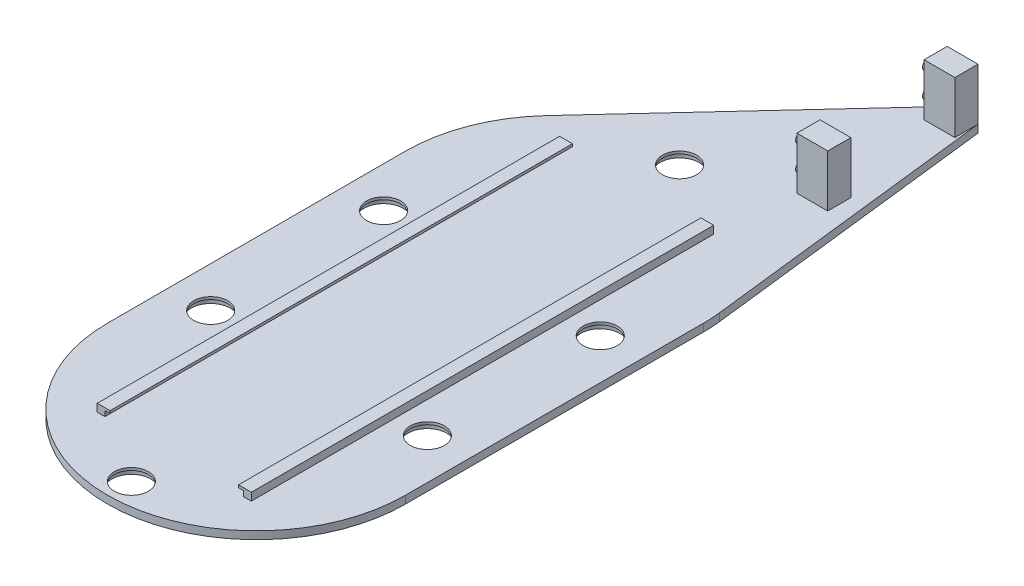
SolidWorks part; units mm, degrees
ref_plane "Front Plane" through (0, 0, 0) normal (0, 0, 1) x (1, 0, 0)
ref_plane "Top Plane" through (0, 0, 0) normal (0, 1, 0) x (1, 0, 0)
ref_plane "Right Plane" through (0, 0, 0) normal (1, 0, 0) x (0, 0, -1)
sketch "Sketch1" plane through (0, 0, 0) normal (0, 1, 0) x (1, 0, 0)
  line L0 (-1000, 0) -> (49000, 0) construction
  line L1 (58, -58) -> (58, 58)
  line L2 (-58, -58) -> (-58, 58)
  circle A0 centre (0, 58) radius 58 construction
  circle A1 centre (0, 106.6995) radius 6.625
  circle A2 centre (42.175, 33.6503) radius 6.625
  circle A3 centre (-42.175, 33.6503) radius 6.625
  circle A4 centre (-42.175, -33.6503) radius 6.625
  circle A5 centre (0, -106.6995) radius 6.625
  circle A6 centre (42.175, -33.6503) radius 6.625
  circle A7 centre (0, -58) radius 58 construction
  arc A8 (58, -58) -> (-58, -58) centre (0, -58) cw
  arc A9 (-58, 58) -> (58, 58) centre (0, 58) cw
  point P12 (0, 58)
  dimension "D1" = 116
  dimension "D2" = 13.25
  dimension "D4" = 84.35
  dimension "D3" = 3
extrude "Boss-Extrude1" add sketch "Sketch1" along normal blind 3
sketch "Sketch2" plane through (0, 0, 0) normal (0, -1, 0) x (1, 0, 0)
  circle A21 centre (42.175, -33.6503) radius 7.6
  circle A22 centre (-42.175, -33.6503) radius 7.6
  circle A23 centre (0, -106.6995) radius 7.6
  circle A24 centre (42.175, 33.6503) radius 7.6
  circle A25 centre (0, 106.6995) radius 7.6
  circle A26 centre (-42.175, 33.6503) radius 7.6
  dimension "D1" = 15.2
extrude "Cut-Extrude1" cut sketch "Sketch2" against normal blind 2
sketch "Sketch3" plane through (0, 0, 0) normal (0, 0, 1) x (1, 0, 0)
  line L0 (58, 3) -> (-58, 3) construction
  line L1 (-25, 5) -> (-27, 5)
  line L2 (30, 3) -> (30, 6)
  line L3 (30, 6) -> (25, 6)
  line L4 (25, 6) -> (25, 5)
  line L5 (25, 5) -> (27, 5)
  line L6 (27, 5) -> (27, 3)
  line L7 (0, 0) -> (0, 25.874) construction
  line L8 (27, 3) -> (30, 3)
  line L9 (-25, 6) -> (-25, 5)
  line L10 (-30, 6) -> (-25, 6)
  line L11 (-30, 3) -> (-30, 6)
  line L12 (-27, 3) -> (-30, 3)
  line L13 (-27, 5) -> (-27, 3)
  dimension "D1" = 60
  dimension "D2" = 3
  dimension "D3" = 2
  dimension "D4" = 1
  dimension "D5" = 2
extrude "Boss-Extrude2" add sketch "Sketch3" along normal mid plane 180
sketch "Sketch4" plane through (0, 0, 0) normal (1, 0, 0) x (0, 0, -1)
  line L0 (149.25, -987.4293) -> (149.25, 49012.5707) construction
  line L9 (129, 23.25) -> (120, 23.25)
  line L10 (129, 23.25) -> (129, 3)
  line L11 (129, 3) -> (120, 3)
  line L12 (120, 23.25) -> (120, 3)
  line L13 (169.5, 23.25) -> (178.5, 23.25)
  line L14 (169.5, 23.25) -> (169.5, 3)
  line L15 (169.5, 3) -> (178.5, 3)
  line L16 (178.5, 23.25) -> (178.5, 3)
  line L17 (-845.7516, 13.125) -> (49154.2484, 13.125) construction
  line L18 (-27.0253, 3) -> (-40.2753, 3) construction
  circle A0 centre (124.55, 8.2125) radius 2.05 construction
  circle A1 centre (124.55, 18.0375) radius 2.05 construction
  circle A2 centre (173.95, 18.0375) radius 2.05 construction
  circle A3 centre (173.95, 8.2125) radius 2.05 construction
  point P19 (169.5, 13.125)
  point P21 (0, 0)
  point P22 (127.9998, 4.384)
  point P23 (129.3281, 7.881)
  dimension "D1" = 4.1
  dimension "D2" = 9.825
  dimension "D3" = 45.3
  dimension "D4" = 40.5
  dimension "D5" = 20.25
  dimension "D6" = 9
  dimension "D7" = 120
ref_plane "Plane1" through (-6.625, 0, 0) normal (1, 0, 0) x (0, 0, -1)
ref_plane "Plane2" through (32.375, 0, 0) normal (1, 0, 0) x (0, 0, -1)
extrude "Boss-Extrude3" add sketch "Sketch4" along normal blind 12 from surface separate body starting at plane "Plane2"
sketch "Sketch5" plane through (32.375, 0, 0) normal (-1, 0, 0) x (0, 0, 1)
  circle A0 centre (-173.95, 8.2125) radius 2.05 construction
  circle A1 centre (-124.55, 8.2125) radius 2.05 construction
  circle A2 centre (-124.55, 18.0375) radius 2.05 construction
  circle A3 centre (-173.95, 8.2125) radius 2.05
  circle A4 centre (-124.55, 8.2125) radius 2.05
  circle A5 centre (-124.55, 18.0375) radius 2.05
  circle A6 centre (-173.95, 18.0375) radius 2.05 construction
  circle A7 centre (-173.95, 18.0375) radius 2.05
extrude "Boss-Extrude4" add sketch "Sketch5" along normal blind 3
sketch "Sketch6" plane through (0, 3, 0) normal (0, 1, 0) x (1, 0, 0)
  line L0 (57.6116, 64.7011) -> (44.375, 178.5)
  line L1 (44.375, 178.5) -> (32.375, 178.5)
  line L2 (32.375, 178.5) -> (-42.5985, 97.362)
  line L3 (44.375, 178.5) -> (32.375, 178.5) construction
  arc A0 (58, 58) -> (-58, 58) centre (0, 58) ccw construction
  arc A1 (57.6116, 64.7011) -> (-42.5985, 97.362) centre (0, 58) ccw
  point P6 (8.375, 178.5)
  point P8 (20.375, 178.5)
  point P12 (20.375, 178.5)
  point P13 (29.8829, 178.5)
extrude "Boss-Extrude5" add sketch "Sketch6" against normal up to surface (3 mm away) up to face at (-42.175, 0, 26.0503)
sketch "Sketch7" plane through (0, 0, 0) normal (1, 0, 0) x (0, 0, -1)
  line L0 (0, -1000) -> (0, 49000) construction
  line L1 (-58, 3) -> (-58, 0) construction
  line L2 (139.2, 13.125) -> (111.3065, 15.5654)
  line L3 (129, 23.25) -> (129, 3) construction
  line L4 (111.3065, 15.5654) -> (81.2, 18.1993)
  line L5 (81.2, 18.1993) -> (-23, 8)
  line L8 (-28, 6) -> (-88, 6)
  line L9 (88, 6) -> (28, 6)
  line L10 (93, 8) -> (197.2, 18.1993)
  line L11 (197.2, 18.1993) -> (167.0935, 15.5654)
  line L12 (167.0935, 15.5654) -> (139.2, 13.125)
  line L13 (178.5, 3) -> (97.362, 3) construction
  line L14 (-23, 8) -> (-23, 6) construction
  line L15 (-23, 6) -> (-28, 6) construction
  line L16 (93, 8) -> (93, 6) construction
  line L17 (93, 6) -> (88, 6) construction
  line L18 (-90, 6) -> (90, 6) construction
  circle A0 centre (-23, 8) radius 1
  circle A1 centre (93, 8) radius 1
  point P0 (-58, 6)
  point P1 (58, 6)
  point P11 (129, 13.125)
  point P15 (58, 6)
  point P27 (-21.1655, 13.4804)
  point P28 (-20.3828, 13.4804)
  point P29 (95.9923, 13.125)
  point P32 (95.5287, 6)
  dimension "D7" = 2
  dimension "D1" = 10.2
  dimension "D2" = 28
  dimension "D3" = 60
  dimension "D4" = 5
  dimension "D5" = 5
  dimension "D6" = 2
  dimension "D8" = 5
  dimension "D9" = 30.2216
  dimension "D10" = 104.698
